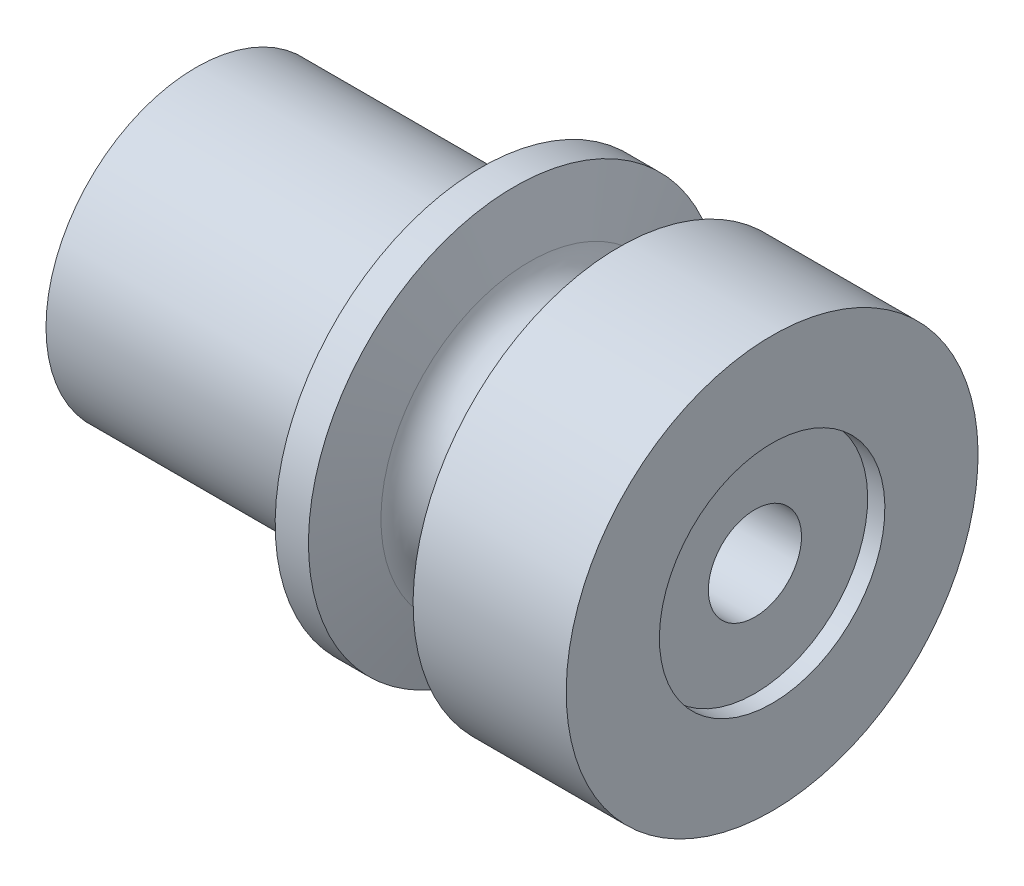
SolidWorks part; units mm, degrees
material "ABS"
ref_plane "Front" through (0, 0, 0) normal (0, 0, 1) x (1, 0, 0)
ref_plane "Top" through (0, 0, 0) normal (0, 1, 0) x (1, 0, 0)
ref_plane "Right" through (0, 0, 0) normal (1, 0, 0) x (0, 0, -1)
ref_axis "side-side" through (80.9, 0, 0) along (-1, 0, 0)
ref_axis "up-down" through (0, 50, 0) along (0, -1, 0)
ref_axis "front-back" through (0, 0, -80.9) along (0, 0, 1)
sketch "Sketch1" plane through (0, 0, 0) normal (0, 0, 1) x (1, 0, 0)
  line L10 (-7.8353, 7.7065) -> (-7.0418, 10.668)
  line L11 (-11.6688, 7.7065) -> (-12.4624, 10.668)
  line L12 (-14.1881, 7.7724) -> (-14.1881, 10.668)
  line L13 (-28.956, 7.7724) -> (-14.1881, 7.7724)
  line L14 (-28.956, 7.7724) -> (-28.956, 6.7564)
  line L15 (-24.6126, 2.413) -> (0, 2.413)
  line L16 (0, 2.413) -> (0, 5.842)
  line L17 (0.892, 5.842) -> (0, 5.842)
  line L18 (0.892, 10.668) -> (0.892, 5.842)
  line L19 (-14.1881, 10.668) -> (-12.4624, 10.668)
  line L20 (-22.5988, 0) -> (8.0828, 0) construction
  line L21 (80.9, 0) -> (-80.9, 0) construction
  line L22 (0, -50) -> (0, 50) construction
  line L23 (-7.0418, 10.668) -> (0.892, 10.668)
  line L24 (-28.956, 6.7564) -> (-24.6126, 2.413)
  arc A1 (-11.6688, 7.7065) -> (-7.8353, 7.7065) centre (-9.7521, 8.2201) ccw
  dimension "D12" = 1.9844
  dimension "D13" = 16.4401
  dimension "D14" = 4.436
  dimension "D1" = 30
  dimension "D2" = 15.5448
  dimension "D3" = 4.826
  dimension "D4" = 11.684
  dimension "D5" = 14.1881
  dimension "D6" = 28.956
  dimension "D7" = 14.7679
  dimension "D8" = 21.336
  dimension "D9" = 45
  dimension "D10" = 1.016
  dimension "D11" = 0.892
revolve "Revolve1" add sketch "Sketch1" angle 360 about L20
